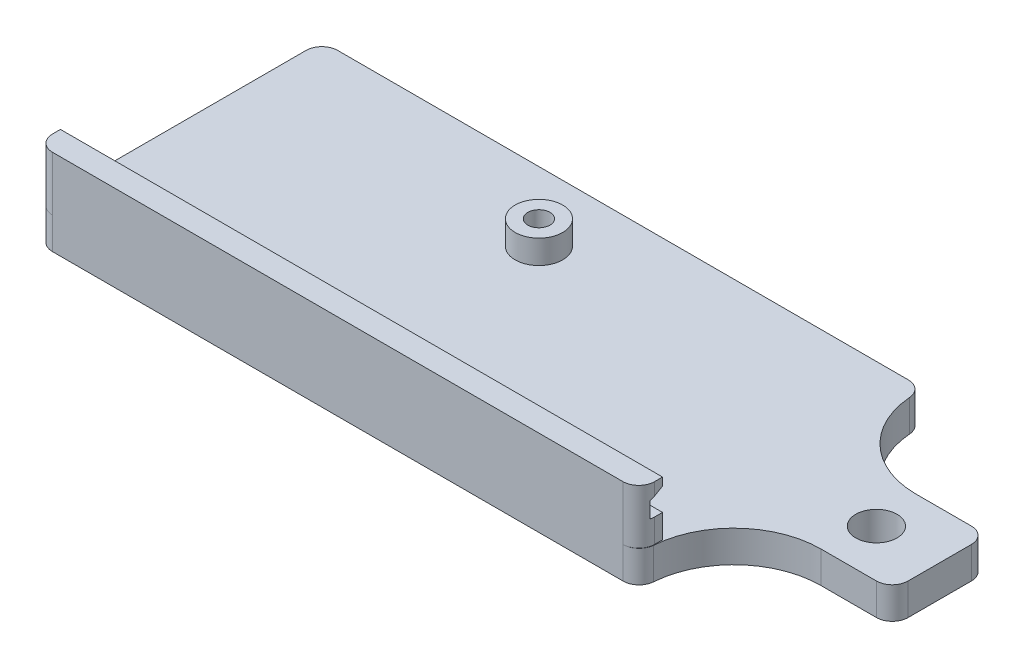
SolidWorks part; units mm, degrees
ref_plane "Front Plane" through (0, 0, 0) normal (0, 0, 1) x (1, 0, 0)
ref_plane "Top Plane" through (0, 0, 0) normal (0, 1, 0) x (1, 0, 0)
ref_plane "Right Plane" through (0, 0, 0) normal (1, 0, 0) x (0, 0, -1)
sketch "Sketch1" plane through (0, 0, 0) normal (0, 1, 0) x (1, 0, 0)
  line L0 (76, -35) -> (76, -36) construction
  line L1 (2, 0) -> (74.0385, 0)
  line L2 (0, -2) -> (0, -34)
  line L3 (2, -36) -> (74.0385, -36)
  line L4 (76, 0) -> (76, -1) construction
  line L5 (87, -12) -> (94, -12)
  line L7 (87, -24) -> (94, -24)
  line L8 (96, -14) -> (96, -22)
  arc A0 (76.0326, -1.8462) -> (87, -12) centre (87, -1) ccw
  arc A1 (87, -24) -> (76.0326, -34.1538) centre (87, -35) ccw
  arc A2 (96, -22) -> (94, -24) centre (94, -22) cw
  arc A3 (96, -14) -> (94, -12) centre (94, -14) ccw
  arc A4 (76.0326, -1.8462) -> (74.0385, 0) centre (74.0385, -2) ccw
  arc A5 (76.0326, -34.1538) -> (74.0385, -36) centre (74.0385, -34) cw
  arc A6 (0, -34) -> (2, -36) centre (2, -34) ccw
  arc A7 (0, -2) -> (2, 0) centre (2, -2) cw
  point P9 (96, -18)
  point P10 (0, -18)
  point P17 (96, -24)
  point P20 (96, -12)
  point P29 (0, -36)
  point P32 (0, 0)
  dimension "D3" = 11
  dimension "D5" = 11
  dimension "D6" = 2
  dimension "D2" = 2
  dimension "D1" = 36
  dimension "D4" = 12
extrude "Boss-Extrude1" add sketch "Sketch1" along normal blind 4
sketch "Sketch2" plane through (0, 0, 0) normal (-1, 0, 0) x (0, 0, 1)
  line L0 (36, 4) -> (36, 10.866)
  line L1 (36, 10.866) -> (33, 10.866)
  line L2 (33, 10.866) -> (33, 9.866)
  line L3 (33, 9.866) -> (34.5, 9)
  line L4 (34.5, 9) -> (34.5, 7)
  line L5 (34.5, 7) -> (33, 7)
  line L6 (33, 7) -> (33, 4)
  line L7 (2, 4) -> (34, 4) construction
  line L8 (33, 4) -> (36, 4)
  dimension "D1" = 2
  dimension "D2" = 1.5
  dimension "D3" = 3
  dimension "D4" = 3
  dimension "D5" = 1
  dimension "D6" = 120
extrude "Boss-Extrude2" add sketch "Sketch2" against normal blind 76
fillet "Fillet1" radius 2 2 edges at (0, 7.433, 36) (76, 7.433, 36)
sketch "Sketch3" plane through (0, 4, 0) normal (0, 1, 0) x (1, 0, 0)
  line L0 (75.9365, -34.5) -> (0.0635, -34.5) construction
  line L1 (3.1, -8.7) -> (72.9, -8.7) construction
  line L3 (76, -33) -> (0, -33) construction
  circle A0 centre (36.1, -8.7) radius 3
  point P10 (38, -33)
  point P11 (38, -8.7)
  dimension "D4" = 6
  dimension "D1" = 25.8
  dimension "D2" = 69.8
  dimension "D3" = 33
extrude "Boss-Extrude3" add sketch "Sketch3" along normal up to surface (3 mm away) up to face at (38, 7, 33.834)
sketch "Sketch4" plane through (0, 4, 0) normal (0, 1, 0) x (1, 0, 0)
  line L0 (96, -22) -> (96, -14) construction
  circle A0 centre (88, -18) radius 2.6
  circle A1 centre (36.1, -8.7) radius 1.4
  point P7 (0, 0)
  point P8 (96, -18)
  dimension "D1" = 2.8
  dimension "D2" = 5.2
  dimension "D3" = 8
extrude "Cut-Extrude1" cut sketch "Sketch4" against normal through all both and the other way through all
